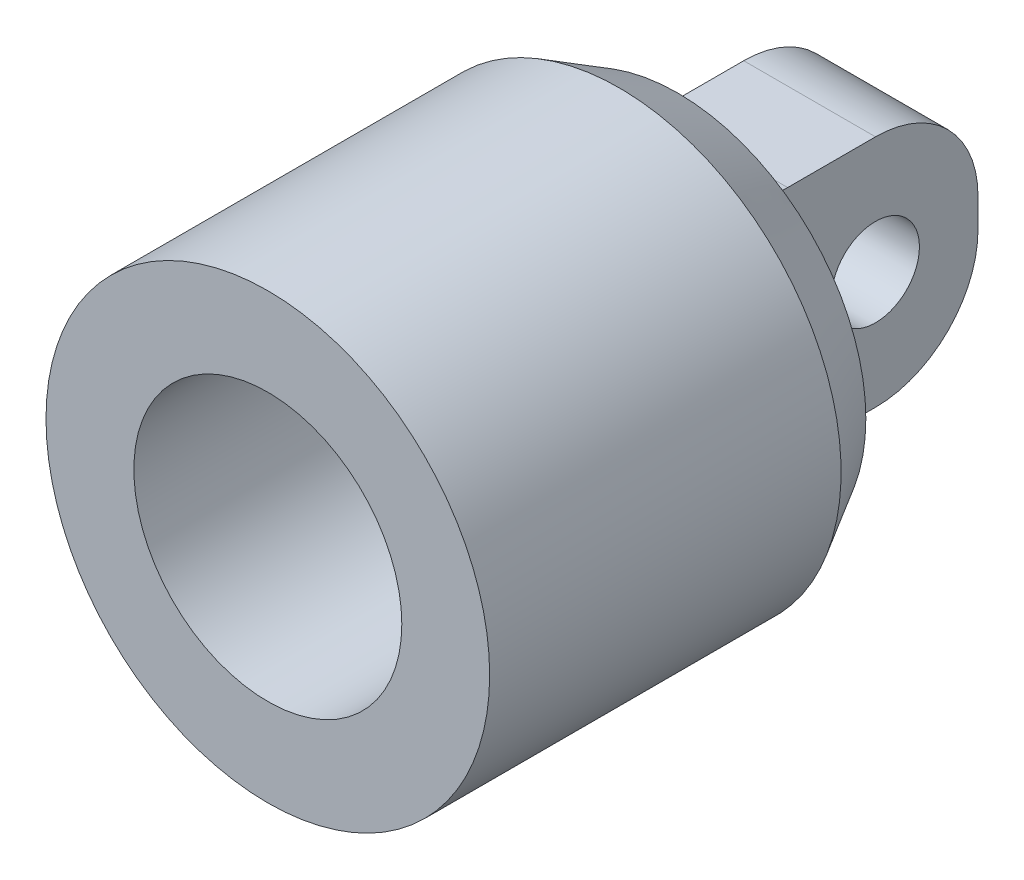
SolidWorks part; units mm, degrees
ref_plane "Front Plane" through (0, 0, 0) normal (0, 0, 1) x (1, 0, 0)
ref_plane "Top Plane" through (0, 0, 0) normal (0, 1, 0) x (1, 0, 0)
ref_plane "Right Plane" through (0, 0, 0) normal (1, 0, 0) x (0, 0, -1)
sketch "Sketch1" plane through (0, 0, 0) normal (0, 0, 1) x (1, 0, 0)
  circle A0 centre (0, 0) radius 4.575
  circle A1 centre (0, 0) radius 7.575
  dimension "D1" = 9.15
  dimension "D2" = 3
extrude "Boss-Extrude1" add sketch "Sketch1" along normal blind 12
sketch "Sketch2" plane through (0, 0, 0) normal (0, 0, -1) x (-1, 0, 0)
  circle A0 centre (0, 0) radius 7.575 construction
  circle A1 centre (0, 0) radius 7.575
extrude "Boss-Extrude2" add sketch "Sketch2" along normal blind 2
sketch "Sketch4" plane through (0, 0, 0) normal (1, 0, 0) x (0, 0, -1)
  line L0 (2, 4) -> (10, 4)
  line L1 (2, -7.575) -> (2, 7.575) construction
  line L2 (10, 4) -> (10, -4)
  line L3 (10, -4) -> (2, -4)
  line L4 (2, -4) -> (2, 4)
  point P4 (2, 0)
  dimension "D1" = 8
  dimension "D2" = 8
extrude "Boss-Extrude3" add sketch "Sketch4" along normal mid plane 4.5
sketch "Sketch5" plane through (2.25, 0, 0) normal (1, 0, 0) x (0, 0, -1)
  circle A0 centre (6.5, 0) radius 1.5
  dimension "D1" = 3
  dimension "D2" = 6.5
extrude "Cut-Extrude1" cut sketch "Sketch5" against normal through all
fillet "Fillet1" radius 3.5 2 edges at (0, 4, -10) (0, -4, -10)
fillet "Fillet2" radius 1.5 2 edges at (0, -4, -2) (0, 4, -2)
fillet "Fillet3" radius 0.8 2 edges at (-2.25, 0, -2) (2.25, 0, -2)
chamfer "Chamfer1" distance 2 angle 30 1 edges at (-7.575, 0, -2) first distance on face at (7.575, 0, 12)
